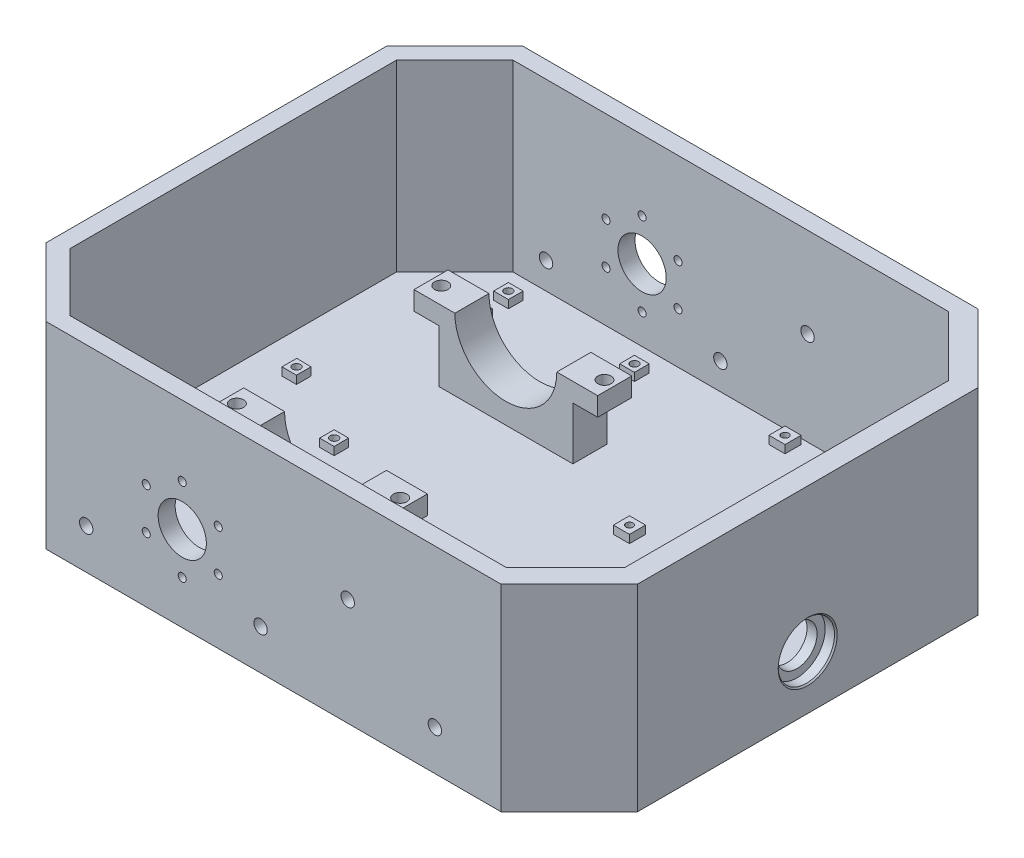
SolidWorks part; units mm, degrees
ref_plane "Front Plane" through (0, 0, 0) normal (0, 0, 1) x (1, 0, 0)
ref_plane "Top Plane" through (0, 0, 0) normal (0, 1, 0) x (1, 0, 0)
ref_plane "Right Plane" through (0, 0, 0) normal (1, 0, 0) x (0, 0, -1)
sketch "Sketch2" plane through (0, 0, 0) normal (0, 1, 0) x (1, 0, 0)
  line L1 (-127, 76.2) -> (63.5, 76.2)
  line L2 (-127, 76.2) -> (-127, -101.6)
  line L3 (-127, -101.6) -> (63.5, -101.6)
  line L4 (63.5, 76.2) -> (63.5, -101.6)
  dimension "D1" = 190.5
  dimension "D2" = 177.8
  dimension "D3" = 76.2
  dimension "D4" = 63.5
extrude "Boss-Extrude1" add sketch "Sketch2" along normal blind 5.08
chamfer "Chamfer1" distance 25.4 angle 45 2 edges at (-127, 2.54, -76.2) (-127, 2.54, 101.6)
sketch "Sketch4" plane through (0, 5.08, 0) normal (0, 1, 0) x (1, 0, 0)
  line L0 (57.15, 69.85) -> (-98.9697, 69.85)
  line L1 (-98.9697, 69.85) -> (-120.65, 48.1697)
  line L2 (-120.65, 48.1697) -> (-120.65, -73.5697)
  line L3 (-120.65, -73.5697) -> (-98.9697, -95.25)
  line L4 (-98.9697, -95.25) -> (57.15, -95.25)
  line L6 (63.5, 76.2) -> (-101.6, 76.2)
  line L7 (-101.6, 76.2) -> (-127, 50.8)
  line L8 (-127, 50.8) -> (-127, -76.2)
  line L9 (-127, -76.2) -> (-101.6, -101.6)
  line L10 (-101.6, -101.6) -> (63.5, -101.6)
  line L11 (63.5, -101.6) -> (63.5, 76.2)
  line L12 (63.5, 76.2) -> (-101.6, 76.2)
  line L13 (-101.6, 76.2) -> (-127, 50.8)
  line L14 (-127, 50.8) -> (-127, -76.2)
  line L15 (-127, -76.2) -> (-101.6, -101.6)
  line L16 (-101.6, -101.6) -> (63.5, -101.6)
  line L17 (63.5, -101.6) -> (63.5, -95.25)
  line L18 (57.15, 69.85) -> (63.5, 69.85)
  line L19 (57.15, -95.25) -> (63.5, -95.25)
  line L20 (63.5, 69.85) -> (63.5, 76.2)
  line L21 (63.5, -101.6) -> (63.5, 76.2) construction
  line L22 (57.15, -95.25) -> (57.15, 69.85) construction
  dimension "D2" = 6.35
  dimension "D1" = 0
extrude "Boss-Extrude3" add sketch "Sketch4" along normal blind 68.42
sketch "Sketch5" plane through (0, 0, 101.6) normal (0, 0, 1) x (1, 0, 0)
  line L0 (-150.3871, 38.1) -> (157.7429, 38.1) construction
  line L1 (-101.6, 0) -> (63.5, 0) construction
  line L2 (0, -14.9262) -> (0, 83.7522) construction
  line L3 (-50.8, 49.8289) -> (-50.8, 11.4994) construction
  line L5 (-71.0506, 31.75) -> (-33.7726, 31.75) construction
  circle A0 centre (-50.8, 31.75) radius 9
  circle A1 centre (-50.8, 31.75) radius 15.5 construction
  circle A2 centre (-50.8, 47.25) radius 1.5
  circle A3 centre (-37.3766, 39.5) radius 1.5
  circle A4 centre (-37.3766, 24) radius 1.5
  circle A5 centre (-50.8, 16.25) radius 1.5
  circle A6 centre (-64.2234, 24) radius 1.5
  circle A7 centre (-64.2234, 39.5) radius 1.5
  dimension "D2" = 18
  dimension "D5" = 31
  dimension "D6" = 3
  dimension "D1" = 38.1
  dimension "D3" = 50.8
  dimension "D4" = 6.35
  dimension "D7" = 6
extrude "Cut-Extrude1" cut sketch "Sketch5" against normal through all
sketch "Sketch10" plane through (63.5, 0, 0) normal (1, 0, 0) x (0, 0, -1)
  line L1 (-101.6, 0) -> (76.2, 0)
  line L2 (-101.6, 0) -> (-101.6, 73.5)
  line L3 (-101.6, 73.5) -> (76.2, 73.5)
  line L4 (76.2, 0) -> (76.2, 73.5)
extrude "Boss-Extrude6" add sketch "Sketch10" along normal blind 30
chamfer "Chamfer3" distance 25.4 angle 45 2 edges at (93.5, 36.75, -76.2) (93.5, 36.75, 101.6)
sketch "Sketch11" plane through (0, 73.5, 0) normal (0, 1, 0) x (1, 0, 0)
  line L0 (63.5, -95.25) -> (85.7572, -72.9928)
  line L1 (85.7572, -72.9928) -> (85.7572, 47.5928)
  line L2 (85.7572, 47.5928) -> (63.5, 69.85)
  line L4 (63.5, -95.25) -> (63.5, 69.85)
  line L5 (85.7572, 47.5928) -> (62.625, 70.725) construction
  line L6 (62.625, -96.125) -> (85.7572, -72.9928) construction
  line L8 (93.5, -76.2) -> (93.5, 50.8)
  line L9 (93.5, 50.8) -> (68.1, 76.2)
  line L10 (68.1, 76.2) -> (-101.6, 76.2)
  line L11 (-101.6, 76.2) -> (-127, 50.8)
  line L12 (-127, 50.8) -> (-127, -76.2)
  line L13 (-127, -76.2) -> (-101.6, -101.6)
  line L14 (-101.6, -101.6) -> (68.1, -101.6)
  line L15 (68.1, -101.6) -> (93.5, -76.2)
  line L16 (93.5, -76.2) -> (93.5, 50.8)
  line L17 (93.5, 50.8) -> (68.1, 76.2)
  line L23 (68.1, -101.6) -> (93.5, -76.2)
  line M22 (63.5, 69.85) -> (63.5, -95.25)
  dimension "D1" = 0
extrude "Cut-Extrude2" cut sketch "Sketch11" along direction (0, 1, 0) on the side against the normal up to surface (68.42 mm away) contours L1 L2 L0 M22 region at (74.0506, 73.5, 12.7) up to face at (-52.0399, 5.08, 12.7)
sketch "Sketch12" plane through (0, 0, 95.25) normal (0, 0, -1) x (-1, 0, 0)
  line L1 (-63.5, 5.08) -> (98.9697, 5.08) construction
  line L2 (25.8, 5.08) -> (75.8, 5.08)
  line L3 (25.8, 5.08) -> (25.8, 31.75)
  line L4 (25.8, 31.75) -> (31.8, 31.75)
  line L5 (75.8, 5.08) -> (75.8, 31.75)
  line L6 (69.8, 31.75) -> (75.8, 31.75)
  arc A0 (31.8, 31.75) -> (69.8, 31.75) centre (50.8, 31.75) ccw
  dimension "D1" = 38
  dimension "D2" = 25
  dimension "D3" = 25
extrude "Boss-Extrude7" add sketch "Sketch12" along normal blind 12.7 from offset 38.1
ref_plane "Plane1" through (0, 0, 12.7) normal (0, 0, 1) x (1, 0, 0)
sketch "Sketch13" plane through (0, 31.75, 0) normal (0, 1, 0) x (1, 0, 0)
  line L0 (-25.8, -44.45) -> (-75.8, -44.45) construction
  line L1 (-31.8, -44.45) -> (-16.56, -44.45)
  line L2 (-31.8, -44.45) -> (-31.8, -57.15)
  line L3 (-31.8, -57.15) -> (-16.56, -57.15)
  line L4 (-16.56, -44.45) -> (-16.56, -57.15)
  line L5 (-31.8, -44.45) -> (-25.8, -44.45) construction
  line L6 (-31.8, -57.15) -> (-25.8, -57.15) construction
  line L7 (-31.8, -44.45) -> (-31.8, -57.15) construction
  dimension "D1" = 15.24
extrude "Boss-Extrude8" add sketch "Sketch13" against normal blind 7
sketch "Sketch14" plane through (0, 31.75, 0) normal (0, 1, 0) x (1, 0, 0)
  line L0 (-31.8, -44.45) -> (-16.56, -44.45) construction
  line L2 (-20.37, -50.8) -> (-20.37, -44.45) construction
  line L3 (-20.37, -50.8) -> (-20.37, -57.15) construction
  line L4 (-31.8, -57.15) -> (-16.56, -57.15) construction
  line L5 (-31.8, -44.45) -> (-31.8, -57.15) construction
  circle A0 centre (-20.37, -50.8) radius 2.5
  dimension "D1" = 5
  dimension "D2" = 11.43
extrude "Cut-Extrude3" cut sketch "Sketch14" against normal blind 10
ref_plane "Plane2" through (-50.8, 0, 0) normal (-1, 0, 0) x (0, 0, 1)
mirror "Mirror2" about plane through (-50.8, 0, 0) normal (-1, 0, 0) of "Boss-Extrude8"
mirror "Mirror3" about plane through (-50.8, 0, 0) normal (-1, 0, 0) of "Cut-Extrude3"
mirror "Mirror4" about plane through (0, 0, 12.7) normal (0, 0, 1) of "Boss-Extrude7", "Boss-Extrude8", "Cut-Extrude3", "Mirror3", "Mirror2"
sketch "Sketch15" plane through (0, 0, 101.6) normal (0, 0, 1) x (1, 0, 0)
  line L0 (-101.6, 0) -> (68.1, 0) construction
  line L1 (-101.6, 73.5) -> (-101.6, 0) construction
  circle A0 centre (-86.6, 15) radius 2.5
  circle A1 centre (-21.6, 15) radius 2.5
  circle A2 centre (43.4, 15) radius 2.5
  circle A3 centre (10.9, 40) radius 2.5
  dimension "D1" = 5
  dimension "D2" = 40
  dimension "D4" = 65
  dimension "D5" = 15
  dimension "D6" = 15
  dimension "D3" = 130
  dimension "D7" = 32.5
extrude "Cut-Extrude4" cut sketch "Sketch15" against normal through all contours A1 | A3 | A2 | A0 region at (-21.6, 15, 101.6) region at (43.4, 15, 101.6) region at (10.9, 40, 101.6)
sketch "Sketch17" plane through (0, 5.08, 0) normal (0, 1, 0) x (1, 0, 0)
  line L0 (-98.9697, 69.85) -> (63.5, 69.85) construction
  line L1 (4.5, 67.85) -> (10.5, 67.85)
  line L2 (4.5, 67.85) -> (4.5, 61.85)
  line L3 (4.5, 61.85) -> (10.5, 61.85)
  line L4 (10.5, 67.85) -> (10.5, 61.85)
  line L5 (4.5, 67.85) -> (10.5, 61.85) construction
  line L6 (4.5, 61.85) -> (10.5, 67.85) construction
  line L7 (59.5, 61.85) -> (53.5, 61.85)
  line L8 (59.5, 61.85) -> (59.5, 67.85)
  line L9 (59.5, 67.85) -> (53.5, 67.85)
  line L10 (53.5, 61.85) -> (53.5, 67.85)
  line L11 (59.5, 61.85) -> (53.5, 67.85) construction
  line L12 (59.5, 67.85) -> (53.5, 61.85) construction
  line L13 (4.5, 9.85) -> (10.5, 9.85)
  line L14 (4.5, 9.85) -> (4.5, 3.85)
  line L15 (4.5, 3.85) -> (10.5, 3.85)
  line L16 (10.5, 9.85) -> (10.5, 3.85)
  line L17 (4.5, 9.85) -> (10.5, 3.85) construction
  line L18 (4.5, 3.85) -> (10.5, 9.85) construction
  line L19 (53.5, 9.85) -> (59.5, 9.85)
  line L20 (53.5, 9.85) -> (53.5, 3.85)
  line L21 (53.5, 3.85) -> (59.5, 3.85)
  line L22 (59.5, 9.85) -> (59.5, 3.85)
  line L23 (53.5, 9.85) -> (59.5, 3.85) construction
  line L24 (53.5, 3.85) -> (59.5, 9.85) construction
  circle A0 centre (7.5, 64.85) radius 1.35
  circle A1 centre (56.5, 64.85) radius 1.35
  circle A2 centre (7.5, 6.85) radius 1.35
  circle A3 centre (56.5, 6.85) radius 1.35
  dimension "D3" = 2.7
  dimension "D1" = 58
  dimension "D2" = 49
  dimension "D4" = 6
  dimension "D5" = 5
  dimension "D6" = 4
extrude "Boss-Extrude9" add sketch "Sketch17" along normal blind 3
sketch "Sketch18" plane through (0, 5.08, 0) normal (0, 1, 0) x (1, 0, 0)
  line L0 (-120.65, -73.5697) -> (-120.65, 48.1697) construction
  line L1 (-108.3746, -1.34) -> (-102.9743, -1.4388)
  line L2 (-108.3746, -1.34) -> (-108.3746, -6.84)
  line L3 (-108.3746, -6.84) -> (-102.9743, -6.84)
  line L4 (-102.9743, -1.4388) -> (-102.9743, -6.84)
  line L5 (-108.3746, -1.34) -> (-102.9743, -6.84) construction
  line L6 (-108.3746, -6.84) -> (-102.9743, -1.4388) construction
  line L7 (-78.3506, -17.4143) -> (-72.9494, -17.4143)
  line L8 (-78.3506, -17.4143) -> (-78.3506, -22.8155)
  line L9 (-78.3506, -22.8155) -> (-72.9494, -22.8155)
  line L10 (-72.9494, -17.4143) -> (-72.9494, -22.8155)
  line L11 (-78.3506, -17.4143) -> (-72.9494, -22.8155) construction
  line L12 (-78.3506, -22.8155) -> (-72.9494, -17.4143) construction
  line L13 (-98.9697, 69.85) -> (63.5, 69.85) construction
  line L14 (-93.4, 62.6) -> (-87.9, 62.6)
  line L15 (-93.4, 62.6) -> (-93.4, 57.1)
  line L16 (-93.4, 57.1) -> (-87.9, 57.1)
  line L17 (-87.9, 62.6) -> (-87.9, 57.1)
  line L18 (-93.4, 62.6) -> (-87.9, 57.1) construction
  line L19 (-93.4, 57.1) -> (-87.9, 62.6) construction
  line L20 (-46.4, 62.6) -> (-40.9, 62.6)
  line L21 (-46.4, 62.6) -> (-46.4, 57.1)
  line L22 (-46.4, 57.1) -> (-40.9, 57.1)
  line L23 (-40.9, 62.6) -> (-40.9, 57.1)
  line L24 (-46.4, 62.6) -> (-40.9, 57.1) construction
  line L25 (-46.4, 57.1) -> (-40.9, 62.6) construction
  line L26 (-46.4, 51.2) -> (-40.9, 51.2)
  line L27 (-46.4, 51.2) -> (-46.4, 45.7)
  line L28 (-46.4, 45.7) -> (-40.9, 45.7)
  line L29 (-40.9, 51.2) -> (-40.9, 45.7)
  line L30 (-46.4, 51.2) -> (-40.9, 45.7) construction
  line L31 (-46.4, 45.7) -> (-40.9, 51.2) construction
  line L32 (-93.4, 51.2) -> (-87.9, 51.2)
  line L33 (-93.4, 51.2) -> (-93.4, 45.7)
  line L34 (-93.4, 45.7) -> (-87.9, 45.7)
  line L35 (-87.9, 51.2) -> (-87.9, 45.7)
  line L36 (-93.4, 51.2) -> (-87.9, 45.7) construction
  line L37 (-93.4, 45.7) -> (-87.9, 51.2) construction
  line L38 (-120.65, -73.5697) -> (-120.65, 48.1697) construction
  circle A0 centre (-105.65, -4.1149) radius 1.5
  circle A1 centre (-75.65, -20.1149) radius 1.5
  circle A2 centre (-90.65, 59.85) radius 1.5
  circle A3 centre (-90.65, 48.45) radius 1.5
  circle A4 centre (-43.65, 48.45) radius 1.5
  circle A5 centre (-43.65, 59.85) radius 1.5
  dimension "D1" = 3
  dimension "D2" = 3
  dimension "D7" = 3
  dimension "D3" = 5.5
  dimension "D4" = 30
  dimension "D5" = 16
  dimension "D6" = 15
  dimension "D8" = 5.5
  dimension "D9" = 10
  dimension "D10" = 30
  dimension "D11" = 47
  dimension "D12" = 11.4
extrude "Boss-Extrude10" add sketch "Sketch18" along normal blind 3
sketch "Sketch19" plane through (0, 5.08, 0) normal (0, 1, 0) x (1, 0, 0)
  line L0 (44.7572, -83.25) -> (50.7572, -89.25) construction
  line L1 (8.0572, -52.55) -> (14.0572, -52.55)
  line L2 (8.0572, -52.55) -> (8.0572, -46.55)
  line L3 (8.0572, -46.55) -> (14.0572, -46.55)
  line L4 (14.0572, -52.55) -> (14.0572, -46.55)
  line L5 (44.7572, -52.55) -> (50.7572, -52.55)
  line L6 (44.7572, -52.55) -> (44.7572, -46.55)
  line L7 (44.7572, -46.55) -> (50.7572, -46.55)
  line L8 (50.7572, -52.55) -> (50.7572, -46.55)
  line L9 (8.0572, -89.25) -> (14.0572, -89.25)
  line L10 (8.0572, -89.25) -> (8.0572, -83.25)
  line L11 (8.0572, -83.25) -> (14.0572, -83.25)
  line L12 (14.0572, -89.25) -> (14.0572, -83.25)
  line L13 (44.7572, -89.25) -> (50.7572, -89.25)
  line L14 (44.7572, -89.25) -> (44.7572, -83.25)
  line L15 (44.7572, -83.25) -> (50.7572, -83.25)
  line L16 (50.7572, -89.25) -> (50.7572, -83.25)
  line L17 (8.0572, -83.25) -> (14.0572, -89.25) construction
  line L18 (8.0572, -46.55) -> (14.0572, -52.55) construction
  line L19 (44.7572, -46.55) -> (50.7572, -52.55) construction
  line L20 (63.5, -95.25) -> (-98.9697, -95.25) construction
  line L21 (85.7572, 47.5928) -> (85.7572, -72.9928) construction
  circle A0 centre (11.0572, -49.55) radius 1.5
  circle A1 centre (47.7572, -49.55) radius 1.5
  circle A2 centre (47.7572, -86.25) radius 1.5
  circle A3 centre (11.0572, -86.25) radius 1.5
  point P24 (0, 0)
  point P25 (47.7572, -86.25)
  point P26 (47.7572, -49.55)
  point P28 (11.0572, -49.55)
  dimension "D6" = 3
  dimension "D1" = 6
  dimension "D2" = 36.7
  dimension "D3" = 36.7
  dimension "D4" = 6
  dimension "D5" = 35
extrude "Boss-Extrude11" add sketch "Sketch19" along normal blind 3
extrude "Cut-Extrude5" cut sketch "Sketch19<2>" against normal blind 10 contours A0 | A1 | A2 | A3 region at (11.0572, 5.08, 49.55) region at (47.7572, 5.08, 49.55) region at (47.7572, 5.08, 86.25) region at (11.0572, 5.08, 86.25)
sketch "Sketch19<2>" plane through (0, 5.08, 0) normal (0, 1, 0) x (1, 0, 0) same geometry as "Sketch19"
extrude "Cut-Extrude6" cut sketch "Sketch17<2>" against normal blind 10 contours A0 | A1 | A3 | A2 region at (7.5, 5.08, -64.85) region at (56.5, 5.08, -64.85) region at (7.5, 5.08, -6.85) region at (56.5, 5.08, -6.85)
sketch "Sketch17<2>" plane through (0, 5.08, 0) normal (0, 1, 0) x (1, 0, 0) same geometry as "Sketch17"
extrude "Cut-Extrude7" cut sketch "Sketch18<2>" against normal blind 10 contours A2 | A3 | A4 | A5 | A1 | A0 region at (-75.65, 5.08, 20.1149) region at (-90.65, 5.08, -59.85) region at (-90.65, 5.08, -48.45) region at (-43.65, 5.08, -48.45) region at (-43.65, 5.08, -59.85)
sketch "Sketch18<2>" plane through (0, 5.08, 0) normal (0, 1, 0) x (1, 0, 0) same geometry as "Sketch18"
sketch "Sketch20" plane through (93.5, 0, 0) normal (1, 0, 0) x (0, 0, -1)
  line L0 (-12.7, 37.631) -> (-12.7, -37.631) construction
  line L1 (-76.2, 0) -> (50.8, 0) construction
  line L3 (-76.2, 0) -> (50.8, 0)
  circle A0 centre (-12.7, 20) radius 7.5
  circle A2 centre (-12.7, 20) radius 10.5
  point P4 (-12.7, 0)
  dimension "D2" = 15
  dimension "D3" = 21
  dimension "D1" = 20
extrude "Cut-Extrude8" cut sketch "Sketch20" against normal blind 10 contours A0 region at (93.5, 20, 12.7)
extrude "Cut-Extrude9" cut sketch "Sketch20<3>" against normal blind 4 contours A2 A0 region at (93.5, 20, 22.903)
sketch "Sketch20<3>" plane through (93.5, 0, 0) normal (1, 0, 0) x (0, 0, -1) same geometry as "Sketch20"
chamfer "Chamfer4" distance 0.5 angle 45 1 edges at (93.5, 20, 2.2)
